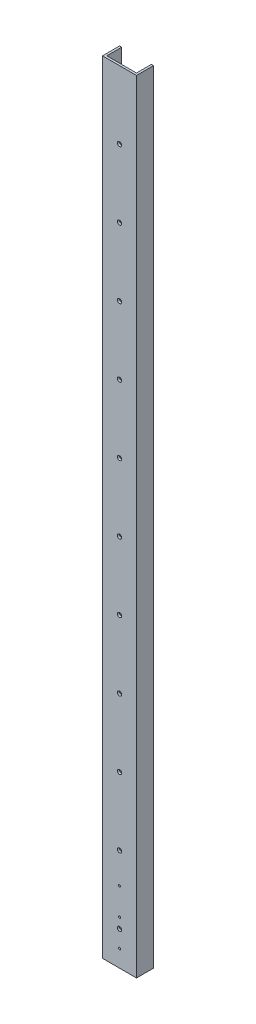
SolidWorks part; units mm, degrees
ref_plane "Front" through (0, 0, 0) normal (0, 0, 1) x (1, 0, 0)
ref_plane "Top" through (0, 0, 0) normal (0, 1, 0) x (1, 0, 0)
ref_plane "Right" through (0, 0, 0) normal (1, 0, 0) x (0, 0, -1)
sketch "Sketch1" plane through (0, 0, 0) normal (0, 1, 0) x (1, 0, 0)
  line L0 (3.175, 3.175) -> (3.175, 25.4)
  line L1 (0, 0) -> (50.8, 0)
  line L2 (0, 0) -> (0, 25.4)
  line L4 (50.8, 0) -> (50.8, 25.4)
  line L5 (3.175, 3.175) -> (47.625, 3.175)
  line L6 (47.625, 3.175) -> (47.625, 25.4)
  line L7 (0, 25.4) -> (3.175, 25.4)
  line L8 (50.8, 25.4) -> (47.625, 25.4)
  dimension "D1" = 25.4
  dimension "D2" = 50.8
  dimension "D3" = 3.175
extrude "Boss-Extrude1" add sketch "Sketch1" along normal blind 1168.4
sketch "Sketch2" plane through (0, 0, 0) normal (0, 0, 1) x (1, 0, 0)
  line L0 (25.4, 0) -> (25.4, 50.8) construction
  line L1 (0, 0) -> (50.8, 0) construction
  circle A0 centre (25.4, 50.8) radius 3.175
  circle A1 centre (25.4, 152.4) radius 3.175
  circle A2 centre (25.4, 254) radius 3.175
  circle A3 centre (25.4, 355.6) radius 3.175
  circle A4 centre (25.4, 457.2) radius 3.175
  circle A5 centre (25.4, 558.8) radius 3.175
  circle A6 centre (25.4, 660.4) radius 3.175
  circle A7 centre (25.4, 762) radius 3.175
  circle A8 centre (25.4, 863.6) radius 3.175
  circle A9 centre (25.4, 965.2) radius 3.175
  circle A10 centre (25.4, 1066.8) radius 3.175
  dimension "D2" = 6.35
  dimension "D1" = 50.8
  dimension "D3" = 11
extrude "Cut-Extrude1" cut sketch "Sketch2" against normal up to next
sketch "Sketch3" plane through (0, 0, -3.175) normal (0, 0, -1) x (-1, 0, 0)
  line L0 (-25.4, 0) -> (-25.4, 25.4) construction
  line L1 (-47.625, 0) -> (-3.175, 0) construction
  circle A0 centre (-25.4, 25.4) radius 1.5875
  circle A3 centre (-25.4, 66.0203) radius 1.5875 construction
  circle A4 centre (-25.4, 66.0203) radius 1.5875
  circle A5 centre (-25.4, 106.6406) radius 1.5875 construction
  circle A6 centre (-25.4, 106.6406) radius 1.5875
  dimension "D2" = 3.175
  dimension "D1" = 25.4
extrude "Cut-Extrude2" cut sketch "Sketch3" against normal up to next
